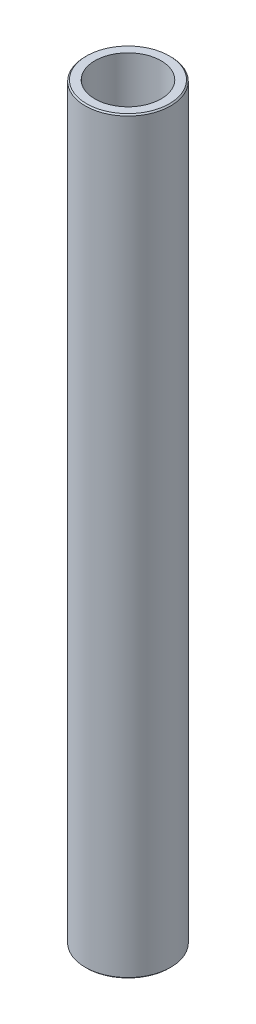
SolidWorks part; units mm, degrees
ref_plane "Front Plane" through (0, 0, 0) normal (0, 0, 1) x (1, 0, 0)
ref_plane "Top Plane" through (0, 0, 0) normal (0, 1, 0) x (1, 0, 0)
ref_plane "Right Plane" through (0, 0, 0) normal (1, 0, 0) x (0, 0, -1)
sketch "Sketch1" plane through (0, 0, 0) normal (0, 1, 0) x (1, 0, 0)
  circle A0 centre (0, 0) radius 25
  dimension "SHAFT_OD" = 50
extrude "Boss-Extrude1" add sketch "Sketch1" along normal blind 438.4415
sketch "Sketch2" plane through (0, 0, 0) normal (0, 1, 0) x (1, 0, 0)
  circle A0 centre (0, 0) radius 19.3936
  dimension "BORE_D" = 38.7873
extrude "Cut-Extrude1" cut sketch "Sketch2" along normal through all
chamfer "Chamfer1" distance 0.7353 angle 45 2 edges at (0, 438.4415, 25) (0, 0, 25)
